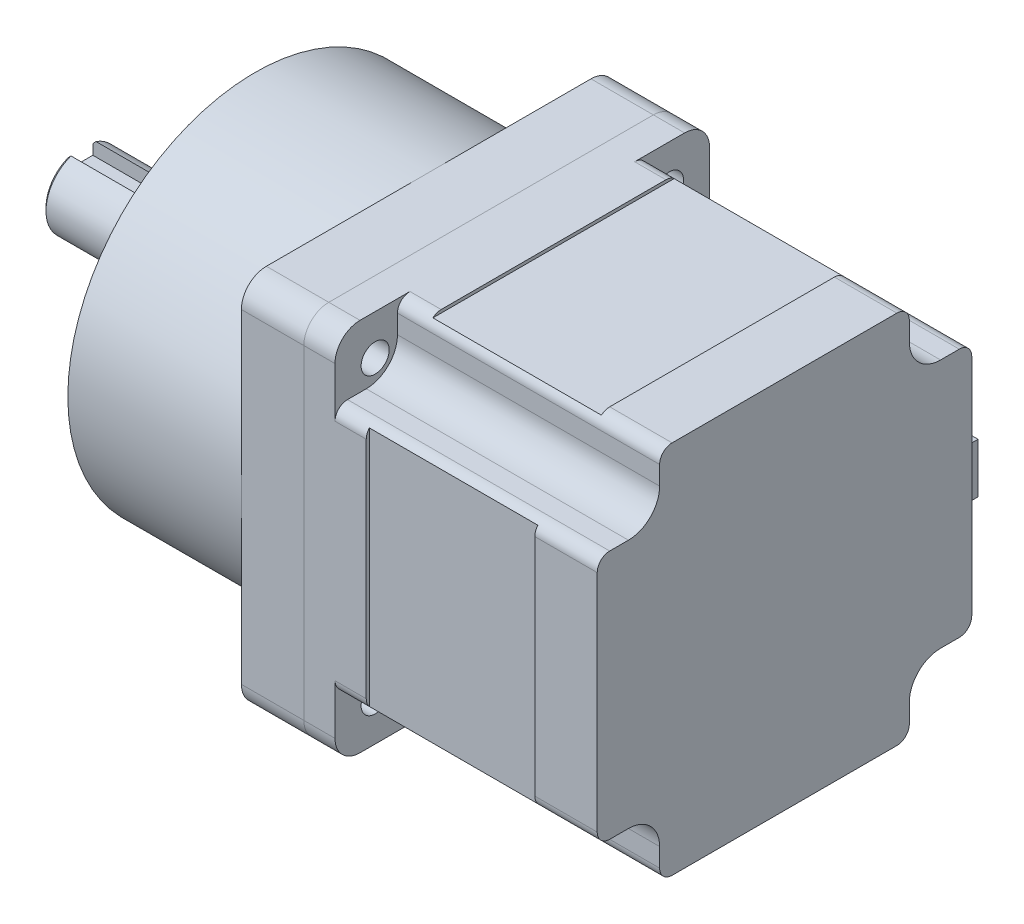
SolidWorks part; units mm, degrees
ref_plane "前视基准面" through (0, 0, 0) normal (0, 0, 1) x (1, 0, 0)
ref_plane "上视基准面" through (0, 0, 0) normal (0, 1, 0) x (1, 0, 0)
ref_plane "右视基准面" through (0, 0, 0) normal (1, 0, 0) x (0, 0, -1)
sketch "草图1" plane through (0, 0, 0) normal (1, 0, 0) x (0, 0, -1)
  line L1 (30, -30) -> (-30, -30)
  line L2 (30, -30) -> (30, 30)
  line L3 (30, 30) -> (-30, 30)
  line L4 (-30, -30) -> (-30, 30)
  line L5 (30, -30) -> (-30, 30) construction
  line L6 (30, 30) -> (-30, -30) construction
  point P0 (0, 0)
  dimension "D1" = 60
  dimension "D2" = 60
extrude "凸台-拉伸1" add sketch "草图1" along normal mid plane 47
sketch "草图7" plane through (0, 0, 0) normal (1, 0, 0) x (0, 0, -1)
  line L1 (29.5, 29.5) -> (-29.5, 29.5)
  line L2 (29.5, 29.5) -> (29.5, -29.5)
  line L3 (29.5, -29.5) -> (-29.5, -29.5)
  line L4 (-29.5, 29.5) -> (-29.5, -29.5)
  line L5 (29.5, 29.5) -> (-29.5, -29.5) construction
  line L6 (29.5, -29.5) -> (-29.5, 29.5) construction
  line L7 (30, -30) -> (-30, -30)
  line L8 (30, -30) -> (30, 30)
  line L9 (30, 30) -> (-30, 30)
  line L10 (-30, -30) -> (-30, 30)
  line L11 (30, -30) -> (-30, 30) construction
  line L12 (30, 30) -> (-30, -30) construction
  point P0 (0, 0)
  point P6 (0, 0)
  dimension "D1" = 59
  dimension "D2" = 59
  dimension "D3" = 60
  dimension "D4" = 60
extrude "切除-拉伸1" cut sketch "草图7" against normal mid plane 27
sketch "草图2" plane through (-23.5, 0, 0) normal (-1, 0, 0) x (0, 0, 1)
  circle A0 centre (0, 0) radius 19.05
  dimension "D1" = 38.1
extrude "凸台-拉伸2" add sketch "草图2" along normal blind 1.6
sketch "草图3" plane through (-25.1, 0, 0) normal (-1, 0, 0) x (0, 0, 1)
  circle A0 centre (0, 0) radius 4
  dimension "D1" = 8
extrude "凸台-拉伸3" add sketch "草图3" along normal blind 22.4
sketch "草图10" plane through (0, 0, -30) normal (0, 0, -1) x (-1, 0, 0)
  line L0 (-23.5, -30) -> (-23.5, 30) construction
  line L1 (-21.5, -4) -> (-18.5, -4)
  line L2 (-21.5, -4) -> (-21.5, 4)
  line L3 (-21.5, 4) -> (-18.5, 4)
  line L4 (-18.5, -4) -> (-18.5, 4)
  line L5 (-21.5, -4) -> (-18.5, 4) construction
  line L6 (-21.5, 4) -> (-18.5, -4) construction
  point P0 (-20, 0)
  dimension "D1" = 8
  dimension "D2" = 3
  dimension "D3" = 2
  dimension "D4" = 0
extrude "凸台-拉伸4" add sketch "草图10" along normal blind 3
sketch "草图14" plane through (-47.5, 0, 0) normal (-1, 0, 0) x (0, 0, 1)
  line L1 (-7.5232, -4.7203) -> (-3.5, -4.7203)
  line L2 (-7.5232, -4.7203) -> (-7.5232, 4.3318)
  line L3 (-7.5232, 4.3318) -> (-3.5, 4.3318)
  line L4 (-3.5, -4.7203) -> (-3.5, 4.3318)
  dimension "D1" = 3.5
extrude "切除-拉伸3" cut sketch "草图14" against normal blind 20
sketch "草图12" plane through (23.5, 0, 0) normal (1, 0, 0) x (0, 0, -1)
  line L1 (30, -30) -> (20, -30)
  line L2 (30, -30) -> (30, -20)
  line L3 (30, -20) -> (20, -20)
  line L4 (20, -30) -> (20, -20)
  line L5 (-30, -30) -> (-20, -30)
  line L6 (-30, -30) -> (-30, -20)
  line L7 (-30, -20) -> (-20, -20)
  line L8 (-20, -30) -> (-20, -20)
  line L9 (-30, 30) -> (-20, 30)
  line L10 (-30, 30) -> (-30, 20)
  line L11 (-30, 20) -> (-20, 20)
  line L12 (-20, 30) -> (-20, 20)
  line L13 (30, 30) -> (20, 30)
  line L14 (30, 30) -> (30, 20)
  line L15 (30, 20) -> (20, 20)
  line L16 (20, 30) -> (20, 20)
  dimension "D1" = 10
  dimension "D2" = 10
  dimension "D3" = 10
  dimension "D4" = 10
  dimension "D5" = 10
  dimension "D6" = 10
  dimension "D7" = 10
  dimension "D8" = 10
extrude "切除-拉伸2" cut sketch "草图12" against normal blind 42
sketch "草图15" plane through (18.5, 0, 0) normal (-1, 0, 0) x (0, 0, 1)
  line L0 (-33, -4) -> (-30, -4) construction
  circle A0 centre (-31.5, -2.5) radius 0.5
  circle A1 centre (-31.5, -1) radius 0.5
  circle A2 centre (-31.5, 0.5) radius 0.5
  circle A3 centre (-31.5, 2) radius 0.5
  dimension "D1" = 1
  dimension "D2" = 1
  dimension "D3" = 1
  dimension "D4" = 1
  dimension "D5" = 1.5
  dimension "D6" = 1.5
  dimension "D7" = 1.5
  dimension "D8" = 1.5
extrude "凸台-拉伸5" add sketch "草图15" along normal blind 10
fillet "圆角2" radius 5 4 edges at (2.5, -20, 20) (2.5, 20, 20) (2.5, 20, -20) (2.5, -20, -20)
fillet "圆角3" radius 2 8 edges at (-16, 30, -20) (-16, 30, 20) (-16, 20, 30) (-16, -20, 30) (-16, -30, 20) (-16, -30, -20) (-16, -20, -30) (-16, 20, -30)
hole_wizard "Ø4.5 (4.5) 直径孔1" positions "草图5" profile "草图4" hole size "Ø4.5" standard "Gb"
sketch "草图5" plane through (-23.5, 0, 0) normal (-1, 0, 0) x (0, 0, 1)
  line L0 (34.65, 0) -> (-34.65, 0) construction
  line L1 (0, -33) -> (0, 33) construction
  point P0 (-23.57, 23.57)
  point P2 (23.57, 23.57)
  point P4 (23.57, -23.57)
  point P6 (-23.57, -23.57)
  dimension "D1" = 47.14
  dimension "D2" = 47.14
  dimension "D3" = 23.57
  dimension "D4" = 23.57
  dimension "D5" = 47.14
  dimension "D6" = 47.14
  dimension "D7" = 23.57
sketch "草图4" plane through (-23.5, 23.57, -23.57) normal (0, 1, 0) x (0, 0, 1)
  line L0 (0, 0) -> (0, 11.3519)
  line L1 (0, 11.3519) -> (2.25, 10)
  line L2 (2.25, 10) -> (2.25, 0)
  line L5 (2.25, 0) -> (0, 0)
  line L10 (0, 11.3519) -> (-2.25, 10) construction
  line L11 (0, -6.35) -> (0, 107.95) construction
  dimension "孔直径" = 4.5
  dimension "孔深度" = 10
  dimension "导头角度" = 118
fillet "圆角1" radius 4 4 edges at (-21, -30, -30) (-21, -30, 30) (-21, 30, -30) (-21, 30, 30)
sketch "草图16" plane through (-23.5, 0, 0) normal (-1, 0, 0) x (0, 0, 1)
  line L0 (-30, -26) -> (-30, 26) construction
  circle A0 centre (0, 0) radius 30
sketch "草图17" plane through (-23.5, 0, 0) normal (-1, 0, 0) x (0, 0, 1)
  line L0 (-30, -26) -> (-30, 26) construction
  line L1 (-26, 30) -> (26, 30) construction
  line L2 (30, 26) -> (30, -26) construction
  line L3 (26, -30) -> (-26, -30) construction
  line L4 (-30, -26) -> (-30, 26)
  line L5 (-26, 30) -> (26, 30)
  line L6 (30, 26) -> (30, -26)
  line L7 (26, -30) -> (-26, -30)
  arc A0 (-26, 30) -> (-30, 26) centre (-26, 26) ccw construction
  arc A1 (30, 26) -> (26, 30) centre (26, 26) ccw construction
  arc A2 (26, -30) -> (30, -26) centre (26, -26) ccw construction
  arc A3 (-30, -26) -> (-26, -30) centre (-26, -26) ccw construction
  circle A4 centre (-23.57, -23.57) radius 2.25 construction
  circle A5 centre (-23.57, 23.57) radius 2.25 construction
  circle A6 centre (23.57, 23.57) radius 2.25 construction
  circle A7 centre (23.57, -23.57) radius 2.25 construction
  arc A8 (-26, 30) -> (-30, 26) centre (-26, 26) ccw
  arc A9 (30, 26) -> (26, 30) centre (26, 26) ccw
  arc A10 (26, -30) -> (30, -26) centre (26, -26) ccw
  arc A11 (-30, -26) -> (-26, -30) centre (-26, -26) ccw
  circle A12 centre (-23.57, -23.57) radius 2.25
  circle A13 centre (-23.57, 23.57) radius 2.25
  circle A14 centre (23.57, 23.57) radius 2.25
  circle A15 centre (23.57, -23.57) radius 2.25
extrude "凸台-拉伸7" add sketch "草图17" along normal blind 10 separate body
sketch "草图18" plane through (-33.5, 0, 0) normal (-1, 0, 0) x (0, 0, 1)
  line L0 (26, 30) -> (-26, 30) construction
  circle A0 centre (0, 0) radius 30
extrude "凸台-拉伸8" add sketch "草图18" along normal blind 27.8
sketch "草图19" plane through (-61.3, 0, 0) normal (-1, 0, 0) x (0, 0, 1)
  circle A0 centre (0, 0) radius 16
  dimension "D1" = 32
extrude "凸台-拉伸9" add sketch "草图19" along normal blind 2
sketch "草图20" plane through (-63.3, 0, 0) normal (-1, 0, 0) x (0, 0, 1)
  circle A0 centre (0, 0) radius 6
  dimension "D1" = 12
extrude "凸台-拉伸10" add sketch "草图20" along normal blind 26
sketch "草图21" plane through (0, 0, 0) normal (0, 1, 0) x (1, 0, 0)
  line L0 (-89.3, 0) -> (-71.3, 0) construction
  line L1 (-89.3, 6) -> (-89.3, -6) construction
  line L2 (-89.3, 2) -> (-71.3, 2)
  line L3 (-89.3, -2) -> (-71.3, -2)
  arc A0 (-89.3, 2) -> (-89.3, -2) centre (-89.3, 0) ccw
  arc A1 (-71.3, -2) -> (-71.3, 2) centre (-71.3, 0) ccw
  point P5 (-80.3, 0)
  dimension "D2" = 20
  dimension "D1" = 4
extrude "切除-拉伸4" cut sketch "草图21" along normal blind 26 from offset 3.5
chamfer "倒角1" distance 0.5 angle 45 1 edges at (-89.3, -6, 0)
sketch "草图22" plane through (-61.3, 0, 0) normal (-1, 0, 0) x (0, 0, 1)
  line L1 (15.9099, -15.9099) -> (-15.9099, -15.9099) construction
  line L2 (15.9099, -15.9099) -> (15.9099, 15.9099) construction
  line L3 (15.9099, 15.9099) -> (-15.9099, 15.9099) construction
  line L4 (-15.9099, -15.9099) -> (-15.9099, 15.9099) construction
  line L5 (15.9099, -15.9099) -> (-15.9099, 15.9099) construction
  line L6 (15.9099, 15.9099) -> (-15.9099, -15.9099) construction
  point P0 (0, 0)
  dimension "D1" = 45
hole_wizard "M5 螺纹孔1" positions "3D草图1" profile "草图23" tap size "M5" standard "Gb"
sketch3d "3D草图1"
  point P0 (-61.3, 15.9099, -15.9099)
  point P3 (-61.3, 15.9099, 15.9099)
  point P6 (-61.3, -15.9099, 15.9099)
  point P9 (-61.3, -15.9099, -15.9099)
sketch "草图23" plane through (-61.3, 15.9099, -15.9099) normal (0, 1, 0) x (0, 0, 1)
  line L0 (0, 0) -> (0, 13.6618)
  line L1 (0, 13.6618) -> (2.1, 12.4)
  line L2 (2.1, 12.4) -> (2.1, 0)
  line L5 (2.1, 0) -> (0, 0)
  line L10 (0, 13.6618) -> (-2.1, 12.4) construction
  line L11 (0, -6.35) -> (0, 107.95) construction
  dimension "螺纹孔钻头直径" = 4.2
  dimension "螺纹孔钻头深度" = 12.4
  dimension "导头角度" = 118
cosmetic thread "孔螺蚊线1" parameters "D1"=10, "D2"=5
cosmetic thread "孔螺蚊线2" parameters "D1"=10, "D2"=5
cosmetic thread "孔螺蚊线3" parameters "D1"=10, "D2"=5
cosmetic thread "孔螺蚊线4" parameters "D1"=10, "D2"=5
